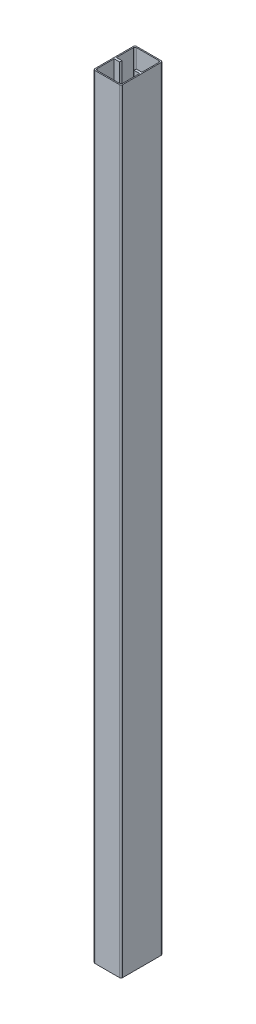
SolidWorks part; units mm, degrees
material "AISI 1045 Aço, trefilado"
ref_plane "Plano frontal" through (0, 0, 0) normal (0, 0, 1) x (1, 0, 0)
ref_plane "Plano superior" through (0, 0, 0) normal (0, 1, 0) x (1, 0, 0)
ref_plane "Plano direito" through (0, 0, 0) normal (1, 0, 0) x (0, 0, -1)
sketch "Esboço1" plane through (0, 0, 0) normal (0, 1, 0) x (1, 0, 0)
  line L0 (-46, 71) -> (-46, 4)
  line L1 (-50, 75) -> (50, 75)
  line L2 (-50, 75) -> (-50, -75)
  line L3 (-50, -75) -> (50, -75)
  line L4 (50, 75) -> (50, -75)
  line L5 (-50, 75) -> (50, -75) construction
  line L6 (-50, -75) -> (50, 75) construction
  line L7 (-46, -71) -> (46, -71)
  line L8 (46, 71) -> (46, 4)
  line L9 (-46, 71) -> (46, 71)
  line L10 (46, -4) -> (46, -71)
  line L11 (-46, 4) -> (-26, 4)
  line L13 (-46, -4) -> (-26, -4)
  line L14 (-26, 4) -> (-26, -4)
  line L15 (46, 4) -> (26, 4)
  line L17 (46, -4) -> (26, -4)
  line L18 (26, 4) -> (26, -4)
  line L19 (46, 71) -> (46, -71) construction
  line L20 (-46, -4) -> (-46, -71)
  line L21 (-46, 71) -> (-46, -71) construction
  point P0 (0, 0)
  dimension "D1" = 150
  dimension "D2" = 100
  dimension "D4" = 8
  dimension "D5" = 8
  dimension "D6" = 4
  dimension "D7" = 4
  dimension "D8" = 20
  dimension "D9" = 20
  dimension "D3" = 4
extrude "Ressalto-extrusão1" add sketch "Esboço1" along normal blind 2782.55
fillet "Filete1" radius 6 8 edges at (-50, 1391.275, -75) (50, 1391.275, 75) (46, 1391.275, 71) (-46, 1391.275, 71) (46, 1391.275, -71) (50, 1391.275, -75) (-50, 1391.275, 75) (-46, 1391.275, -71)
